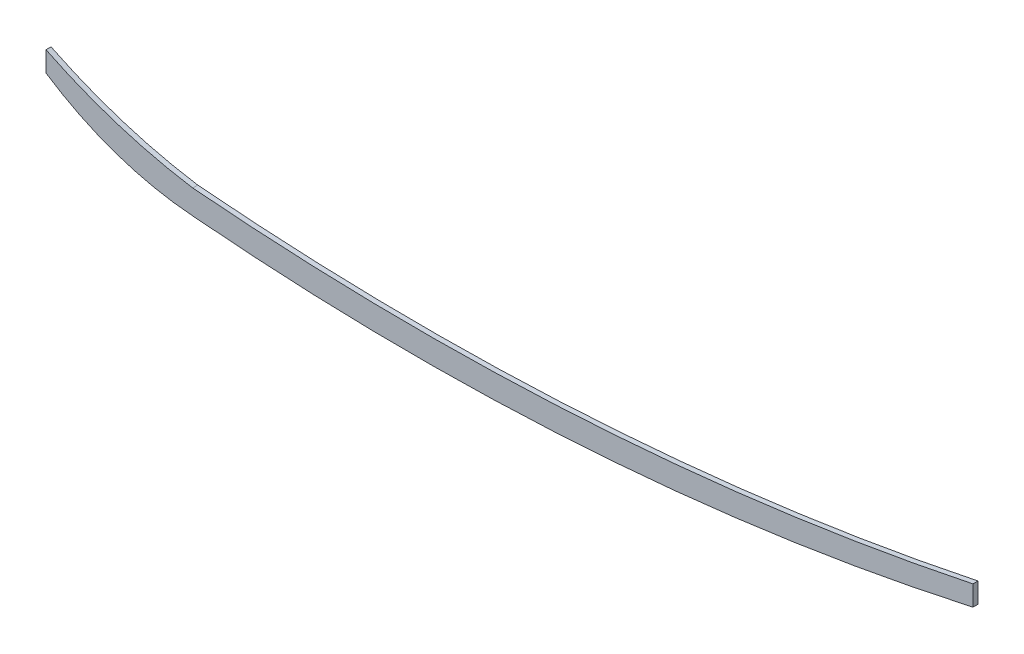
SolidWorks part; units mm, degrees
material "Balsa"
ref_plane "Front Plane" through (0, 0, 0) normal (0, 0, 1) x (1, 0, 0)
ref_plane "Top Plane" through (0, 0, 0) normal (0, 1, 0) x (1, 0, 0)
ref_plane "Right Plane" through (0, 0, 0) normal (1, 0, 0) x (0, 0, -1)
sketch "Sketch1" plane through (0, 0, 0) normal (0, 0, 1) x (1, 0, 0)
  line L3 (0, -97.563) -> (0, -84.863)
  line L4 (583.5225, -97.0036) -> (583.5225, -84.3036)
  arc A6 (0, -97.563) -> (92.3925, -129.289) centre (106.9176, 63.4069) ccw
  arc A10 (92.3925, -129.289) -> (583.5225, -97.0036) centre (233.5795, 1474.6667) ccw
  arc A17 (0, -84.863) -> (92.3925, -114.049) centre (142.0237, 203.9001) ccw
  arc A19 (92.3925, -114.049) -> (583.5225, -84.3036) centre (236.5524, 1575.136) ccw
  dimension "D1" = 193.2426
  dimension "D5" = 1610.1576
  dimension "D6" = 583.5225
  dimension "D4" = 31.726
  dimension "D10" = 15.24
  dimension "D11" = 321.7994
  dimension "D12" = 1695.3253
  dimension "D2" = 97.563
  dimension "D3" = 92.3925
  dimension "D7" = 97.0036
  dimension "D8" = 12.7
  dimension "D9" = 12.7
extrude "Boss-Extrude1" add sketch "Sketch1" along normal mid plane 3.175 contours A19 A17 L3 A6 A10 L4 region at (5.8576, -91.213, 0)
equation "\"slotwidth\"=0.197118"
